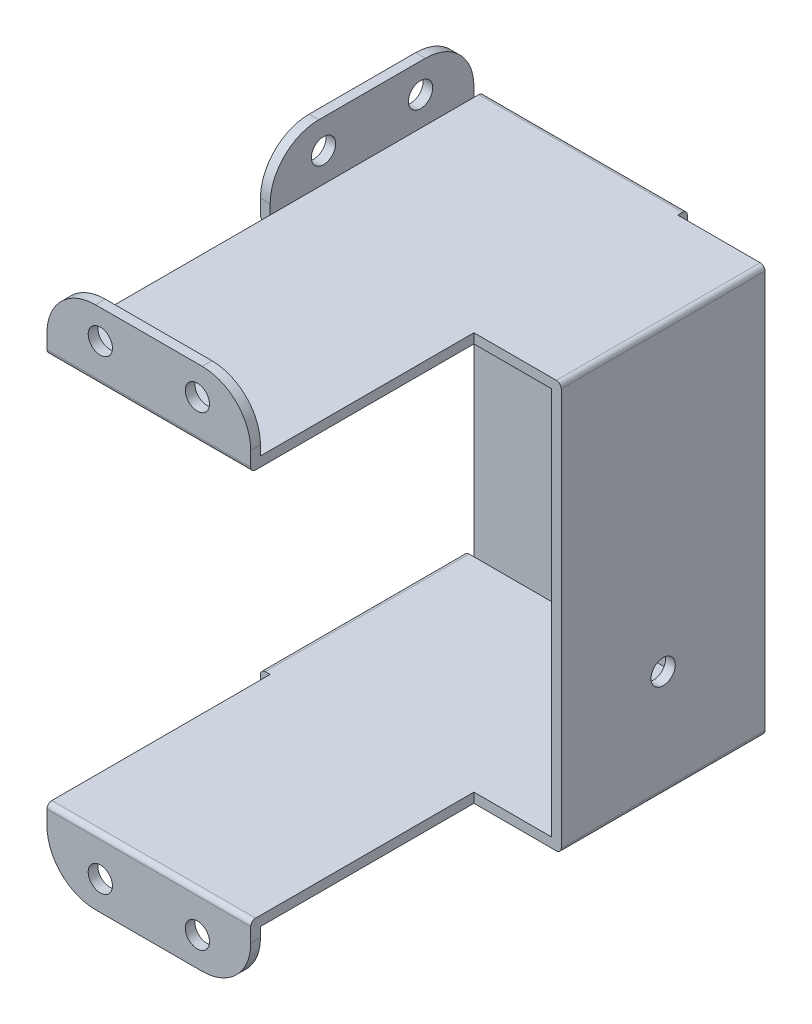
SolidWorks part; units mm, degrees
ref_plane "前视基准面" through (0, 0, 0) normal (0, 0, 1) x (1, 0, 0)
ref_plane "上视基准面" through (0, 0, 0) normal (0, 1, 0) x (1, 0, 0)
ref_plane "右视基准面" through (0, 0, 0) normal (1, 0, 0) x (0, 0, -1)
sketch "草图1" plane through (0, 0, 0) normal (0, 1, 0) x (1, 0, 0)
  line L0 (0, 0) -> (-31, 0)
  line L1 (-31, 0) -> (-31, 21)
  line L2 (-31, 21) -> (0, 21)
  line L3 (0, 21) -> (0, 0)
  dimension "D1" = 21
  dimension "D2" = 31
extrude "凸台-拉伸1" add sketch "草图1" along normal blind 42
shell "抽壳1" thickness 1 removed face at (-15.5, 21, -21) removed face at (-31, 21, -10.5) removed face at (-15.5, 21, 0)
sketch "草图2" plane through (0, 42, 0) normal (0, 1, 0) x (1, 0, 0)
  line L0 (-26, 21) -> (-26, 0)
  line L1 (0, 21) -> (-31, 21) construction
  line L2 (-31, 0) -> (0, 0) construction
  line L3 (-26, 0) -> (-31, 0)
  line L4 (-31, 0) -> (-31, 21)
  line L5 (-31, 21) -> (-26, 21)
  dimension "D1" = 5
extrude "凸台-拉伸2" add sketch "草图2" along normal blind 6
shell "抽壳2" thickness 1 removed face at (-17.8, 26.4, -21) removed face at (-17.8, 26.4, 0) removed face at (-26, 45, -10.5) removed face at (-28.5, 48, -10.5)
sketch "草图3" plane through (0, 0, 0) normal (0, -1, 0) x (1, 0, 0)
  line L0 (-31, 0) -> (-26, 0)
  line L1 (-31, 0) -> (0, 0) construction
  line L2 (-26, 0) -> (-26, -21)
  line L3 (0, -21) -> (-31, -21) construction
  line L4 (-26, -21) -> (-31, -21)
  line L5 (-31, -21) -> (-31, 0)
  dimension "D1" = 5
extrude "凸台-拉伸3" add sketch "草图3" along normal blind 6
shell "抽壳3" thickness 1 removed face at (-19.8333, 21, -21) removed face at (-28.5, -6, -10.5) removed face at (-26, -3, -10.5) removed face at (-19.8333, 21, 0)
sketch "草图4" plane through (0, 0, 0) normal (0, 0, 1) x (1, 0, 0)
  line L0 (-30, 42) -> (-30, 41)
  line L1 (-31, 41) -> (-1, 41) construction
  line L2 (-30, 41) -> (-9, 41)
  line L3 (-9, 41) -> (-9, 42)
  line L4 (-30, 42) -> (0, 42) construction
  line L5 (-9, 42) -> (-30, 42)
  line L6 (-30, 0) -> (-30, 1)
  line L7 (-31, 1) -> (-1, 1) construction
  line L8 (-30, 1) -> (-9, 1)
  line L9 (-9, 1) -> (-9, 0)
  line L10 (-30, 0) -> (0, 0) construction
  line L11 (-9, 0) -> (-30, 0)
  dimension "D1" = 21
  dimension "D2" = 21
extrude "凸台-拉伸4" add sketch "草图4" along normal blind 23
sketch "草图5" plane through (0, 42, 0) normal (0, 1, 0) x (1, 0, 0)
  line L0 (-30, -23) -> (-9, -23)
  line L1 (-9, -23) -> (-9, -18)
  line L2 (-9, -23) -> (-9, 0) construction
  line L3 (-9, -18) -> (-30, -18)
  line L4 (-30, -23) -> (-30, 0) construction
  line L5 (-30, -18) -> (-30, -23)
  dimension "D1" = 5
extrude "凸台-拉伸5" add sketch "草图5" along normal blind 6
shell "抽壳4" thickness 1 removed face at (-19.5, 45, 18) removed face at (-30, 43.6667, 13.6667) removed face at (-9, 43.6667, 13.6667) removed face at (-19.5, 48, 20.5)
sketch "草图6" plane through (0, 0, 0) normal (0, -1, 0) x (1, 0, 0)
  line L0 (-30, 23) -> (-9, 23)
  line L1 (-9, 23) -> (-9, 18)
  line L2 (-9, 23) -> (-9, 0) construction
  line L3 (-9, 18) -> (-30, 18)
  line L4 (-30, 23) -> (-30, 0) construction
  line L5 (-30, 18) -> (-30, 23)
  dimension "D1" = 5
extrude "凸台-拉伸6" add sketch "草图6" along normal blind 6
shell "抽壳5" thickness 1 removed face at (-30, -1.6667, 13.6667) removed face at (-19.5, -3, 18) removed face at (-19.5, -6, 20.5) removed face at (-9, -1.6667, 13.6667)
ref_plane "基准面1" through (-30, 42, -21) normal (-1, 0, 0) x (0, 0, 1)
sketch "草图8" plane through (0, 0, -21) normal (0, 0, -1) x (-1, 0, 0)
  line L0 (30, 42) -> (30, 0)
  line L1 (30, 39.525) -> (30, 44.475) construction
  line L2 (30, 42) -> (9, 42) construction
  line L3 (30, 0) -> (9, 0)
  line L4 (9, 0) -> (9, 42)
  line L5 (0, 42) -> (30, 42) construction
  line L6 (9, 42) -> (30, 42)
extrude "凸台-拉伸7" add sketch "草图8" along normal blind 1
hole_wizard "M3 螺纹孔1" positions "草图9" profile "草图11" tap size "M3" standard "GB" end condition up to next
sketch "草图9" plane through (0, 0, 23) normal (0, 0, 1) x (1, 0, 0)
  line L0 (-9, -6) -> (-30, -6) construction
  line L1 (-30, 48) -> (-9, 48) construction
  point P0 (-24.5, 45)
  point P2 (-14.5, 45)
  point P4 (-24.5, -3)
  point P6 (-14.5, -3)
  point P18 (-19.5, 48)
  dimension "D1" = 3
  dimension "D2" = 3
  dimension "D3" = 5
  dimension "D4" = 5
sketch "草图11" plane through (-24.5, 45, 23) normal (1, 0, 0) x (0, -1, 0)
  line L0 (0, 0) -> (0, 1)
  line L1 (0, 1) -> (1.25, 1)
  line L2 (1.25, 1) -> (1.25, 0)
  line L5 (1.25, 0) -> (0, 0)
  line L11 (0, -6.35) -> (0, 107.95) construction
  dimension "通孔螺纹孔钻头直径" = 2.5
  dimension "通孔螺纹孔钻头深度" = 1
cosmetic thread "孔螺蚊线1" parameters "D2"=3
cosmetic thread "孔螺蚊线2" parameters "D2"=3
cosmetic thread "孔螺蚊线3" parameters "D2"=3
cosmetic thread "孔螺蚊线4" parameters "D2"=3
hole_wizard "M3 螺纹孔2" positions "草图12" profile "草图13" tap size "M3" standard "GB" end condition up to next
sketch "草图12" plane through (-31, 0, 0) normal (-1, 0, 0) x (0, 0, 1)
  line L0 (-21, 48) -> (0, 48) construction
  line L1 (0, -6) -> (-21, -6) construction
  point P0 (-5.5, 45)
  point P2 (-15.5, 45)
  point P4 (-15.5, -3)
  point P6 (-5.5, -3)
  point P19 (-10.5, -6)
  point P20 (-10.5, 48)
  dimension "D1" = 3
  dimension "D2" = 3
  dimension "D3" = 5
  dimension "D4" = 5
  dimension "D5" = 5
sketch "草图13" plane through (-31, 45, -5.5) normal (0, 1, 0) x (0, 0, 1)
  line L0 (0, 0) -> (0, 1)
  line L1 (0, 1) -> (1.25, 1)
  line L2 (1.25, 1) -> (1.25, 0)
  line L5 (1.25, 0) -> (0, 0)
  line L11 (0, -6.35) -> (0, 107.95) construction
  dimension "通孔螺纹孔钻头直径" = 2.5
  dimension "通孔螺纹孔钻头深度" = 1
cosmetic thread "孔螺蚊线5" parameters "D2"=3
cosmetic thread "孔螺蚊线6" parameters "D2"=3
cosmetic thread "孔螺蚊线7" parameters "D2"=3
cosmetic thread "孔螺蚊线8" parameters "D2"=3
hole_wizard "M3 螺纹孔3" positions "草图14" profile "草图15" tap size "M3" standard "GB" end condition up to next
sketch "草图14" plane through (0, 0, 0) normal (1, 0, 0) x (0, 0, -1)
  line L1 (21, 42) -> (0, 42) construction
  line L2 (0, 0) -> (21, 0) construction
  point P0 (10.5, 11)
  point P7 (10.5, 42)
  dimension "D1" = 11
sketch "草图15" plane through (0, 11, -10.5) normal (0, 1, 0) x (0, 0, -1)
  line L0 (0, 0) -> (0, 1)
  line L1 (0, 1) -> (1.25, 1)
  line L2 (1.25, 1) -> (1.25, 0)
  line L5 (1.25, 0) -> (0, 0)
  line L11 (0, -6.35) -> (0, 107.95) construction
  dimension "通孔螺纹孔钻头直径" = 2.5
  dimension "通孔螺纹孔钻头深度" = 1
cosmetic thread "孔螺蚊线9" parameters "D2"=3
hole_wizard "M3 螺纹孔4" positions "草图16" profile "草图17" tap size "M3" standard "GB" end condition up to next
sketch "草图16" plane through (0, 0, -22) normal (0, 0, -1) x (-1, 0, 0)
  line L0 (30, 42) -> (9, 42) construction
  line L1 (9, 0) -> (30, 0) construction
  point P0 (19.5, 11)
  point P5 (19.5, 42)
  dimension "D1" = 11
sketch "草图17" plane through (-19.5, 11, -22) normal (1, 0, 0) x (0, 1, 0)
  line L0 (0, 0) -> (0, 1)
  line L1 (0, 1) -> (1.25, 1)
  line L2 (1.25, 1) -> (1.25, 0)
  line L5 (1.25, 0) -> (0, 0)
  line L11 (0, -6.35) -> (0, 107.95) construction
  dimension "通孔螺纹孔钻头直径" = 2.5
  dimension "通孔螺纹孔钻头深度" = 1
cosmetic thread "孔螺蚊线10" parameters "D2"=3
fillet "圆角2" radius 0.5 8 edges at (-31, 1, -10.5) (-31, 41, -10.5) (-19.5, 1, 23) (-19.5, 41, 23) (-19.5, 0, -22) (-19.5, 42, -22) (0, 0, -10.5) (0, 42, -10.5)
fillet "圆角3" radius 5 8 edges at (-30.5, -6, -21) (-30.5, -6, 0) (-30, -6, 22.5) (-9, -6, 22.5) (-9, 48, 22.5) (-30, 48, 22.5) (-30.5, 48, -21) (-30.5, 48, 0)
